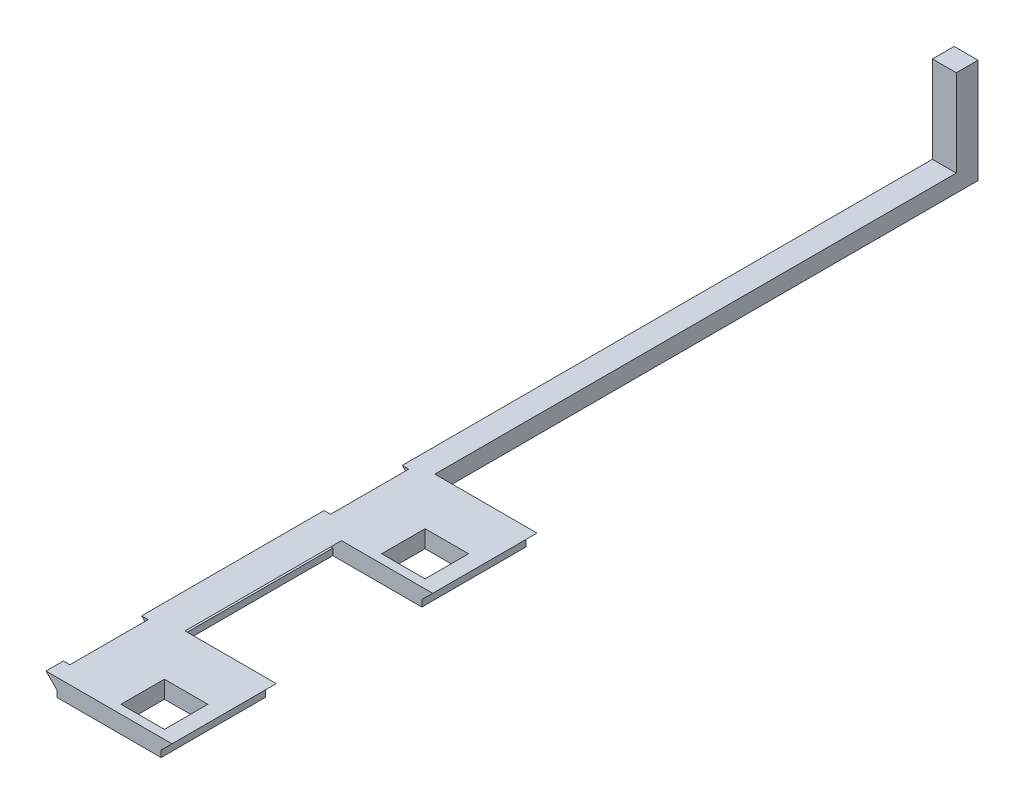
SolidWorks part; units mm, degrees
ref_plane "Płaszczyzna przednia" through (0, 0, 0) normal (0, 0, 1) x (1, 0, 0)
ref_plane "Płaszczyzna górna" through (0, 0, 0) normal (0, 1, 0) x (1, 0, 0)
ref_plane "Płaszczyzna prawa" through (0, 0, 0) normal (1, 0, 0) x (0, 0, -1)
sketch "Szkic6" plane through (0, 0, 0) normal (0, 1, 0) x (1, 0, 0)
  line L0 (9.5, 60) -> (31, 60)
  line L3 (9.5, 24) -> (31, 24)
  line L4 (31, 0) -> (31, 24)
  line L5 (20.25, 24) -> (20.25, 0) construction
  line L6 (2.5, 12) -> (31, 12) construction
  line L9 (31, 60) -> (31, 84)
  line L10 (20.25, 84) -> (20.25, 60) construction
  line L11 (2.5, 72) -> (31, 72) construction
  line L12 (9.5, 60) -> (9.5, 24)
  line L16 (0, 84) -> (0, 0)
  line L17 (6.5, 209) -> (6.5, 84)
  line L18 (6.5, 84) -> (31, 84)
  line L19 (0, 0) -> (31, 0)
  line L21 (0, 84) -> (0, 209)
  line L22 (0, 209) -> (6.5, 209)
  line L25 (0, 146.5) -> (9, 146.5) construction
  line L26 (9.5, 84) -> (31, 84) [skipped]
  point P14 (20.25, 72)
  point P68 (20.25, 12)
  point P281 (4.5, 42)
  point P384 (4.5, 146.5)
  dimension "D1" = 24
  dimension "D2" = 9.5
  dimension "D4" = 60
  dimension "D5" = 31
  dimension "D6" = 209
  dimension "D7" = 6.5
  dimension "D3" = 2
extrude "Dodanie-wyciągnięcie4" add sketch "Szkic6" along normal blind 3
chamfer "Sfazowanie2" distance 3 angle 45 3 edges at (9.5, 0, -42) (31, 0, -72) (31, 0, -12)
fillet "Sfazowanie3" radius 3 1 edges at (0, 0, -104.5) profile chamfer
chamfer "Chamfer1" [suppressed] distance 2 angle 45
sketch "Szkic8" plane through (0, 3, 0) normal (0, 1, 0) x (1, 0, 0)
  line L0 (26.25, 12) -> (26.25, 2)
  line L1 (16.25, 12) -> (16.25, 2)
  line L2 (16.25, 62) -> (26.25, 62)
  line L3 (26.25, 72) -> (16.25, 72)
  line L4 (26.25, 72) -> (26.25, 62)
  line L5 (16.25, 72) -> (16.25, 62)
  line L6 (16.25, 2) -> (26.25, 2)
  line L7 (26.25, 12) -> (16.25, 12)
  line L8 (21.25, 72) -> (21.25, 2) construction
  line L9 (0, 209) -> (0, 0) construction
  line L10 (0, 0) -> (31, 0) construction
  dimension "D1" = 21.25
  dimension "D2" = 10
  dimension "D3" = 10
  dimension "D4" = 60
  dimension "D5" = 2
extrude "Wytnij-wyciągnięcie1" cut sketch "Szkic8" against normal blind 10
sketch "Szkic9" plane through (0, 3, 0) normal (0, 1, 0) x (1, 0, 0)
  line L0 (0, 67) -> (0, 7) construction
  line L2 (0, 67) -> (0, 69) construction
  line L3 (2.5, 82) -> (-2.5, 82)
  line L4 (2.5, 82) -> (2.5, 64)
  line L5 (2.5, 64) -> (-2.5, 64)
  line L6 (-2.5, 82) -> (-2.5, 64)
  line L7 (2.5, 82) -> (-2.5, 64) construction
  line L8 (2.5, 64) -> (-2.5, 82) construction
  line L9 (0, 67) -> (0, 65) construction
  line L10 (0, 7) -> (0, 5) construction
  line L11 (2.5, 22) -> (-2.5, 22)
  line L12 (2.5, 22) -> (2.5, 4)
  line L13 (2.5, 4) -> (-2.5, 4)
  line L14 (-2.5, 22) -> (-2.5, 4)
  line L15 (2.5, 22) -> (-2.5, 4) construction
  line L16 (2.5, 4) -> (-2.5, 22) construction
  line L17 (0, 7) -> (0, 9) construction
  line L18 (0, 209) -> (0, 0) construction
  line L19 (0, 0) -> (31, 0) construction
  circle A2 centre (0, 7) radius 2 construction
  circle A3 centre (0, 67) radius 2 construction
  point P7 (0, 73)
  point P12 (0, 13)
  point P19 (0, 0)
  dimension "D5" = 4
  dimension "D1" = 60
  dimension "D2" = 7
  dimension "D4" = 1
  dimension "D6" = 5
  dimension "D7" = 13
  dimension "D8" = 5
  dimension "D9" = 1
  dimension "D10" = 13
extrude "Wytnij-wyciągnięcie2" cut sketch "Szkic9" against normal blind 10
sketch "Szkic11" plane through (0, 0, 0) normal (0, -1, 0) x (1, 0, 0)
  line L0 (3.5, 0) -> (3.5, -209)
  line L1 (3, 0) -> (28, 0) construction
  line L2 (6.5, -209) -> (3, -209) construction
  line L3 (3.5, -209) -> (6.5, -209)
  line L4 (6.5, -209) -> (6.5, -84)
  line L5 (6.5, -84) -> (27.5, -84)
  line L6 (28, -84) -> (6.5, -84) construction
  line L7 (27.5, -84) -> (27.5, -60)
  line L8 (6.5, -60) -> (28, -60) construction
  line L9 (27.5, -60) -> (7, -60)
  line L10 (7, -60) -> (7, -24)
  line L11 (7, -24) -> (27.5, -24)
  line L12 (28, -24) -> (6.5, -24) construction
  line L13 (27.5, -24) -> (27.5, 0)
  line L14 (27.5, 0) -> (3.5, 0)
  line L15 (6.5, -24) -> (9.5, -24) construction
  line L17 (28, -24) -> (28, 0) construction
  line L19 (28, -84) -> (28, -60) construction
  line L21 (26.25, -12) -> (26.25, -2) construction
  line L22 (26.25, -2) -> (16.25, -2) construction
  line L23 (16.25, -2) -> (16.25, -12) construction
  line L24 (16.25, -12) -> (26.25, -12) construction
  line L25 (26.25, -72) -> (26.25, -62) construction
  line L26 (26.25, -62) -> (16.25, -62) construction
  line L27 (16.25, -62) -> (16.25, -72) construction
  line L28 (16.25, -72) -> (26.25, -72) construction
  line L29 (26.25, -12) -> (26.25, -2)
  line L30 (26.25, -2) -> (16.25, -2)
  line L31 (16.25, -2) -> (16.25, -12)
  line L32 (16.25, -12) -> (26.25, -12)
  line L33 (26.25, -72) -> (26.25, -62)
  line L34 (26.25, -62) -> (16.25, -62)
  line L35 (16.25, -62) -> (16.25, -72)
  line L36 (16.25, -72) -> (26.25, -72)
  point P23 (7, -24)
  point P27 (7, -84)
  dimension "D1" = 3.5
  dimension "D2" = 0.5
  dimension "D4" = 0.5
extrude "Dodanie-wyciągnięcie6" add sketch "Szkic11" along normal blind 1.5
sketch "Szkic13" plane through (0, 0, 0) normal (0, 0, 1) x (1, 0, 0)
  line L0 (3.5, 0) -> (1, 2.5)
  line L1 (1, 2.5) -> (30, 2.5)
  line L2 (30, 2.5) -> (27.5, 0)
  line L3 (0, 3) -> (3, 0) construction
  line L4 (28, 0) -> (31, 3) construction
  line L5 (0, 3) -> (31, 3) construction
  line L6 (3.5, 0) -> (3, 0)
  line L7 (3, 0) -> (0, 3)
  line L8 (0, 3) -> (31, 3)
  line L9 (31, 3) -> (28, 0)
  line L10 (28, 0) -> (27.5, 0)
  dimension "D1" = 0.5
extrude "Wytnij-wyciągnięcie3" cut sketch "Szkic13" against normal blind 270.5 contours L10 L2 L1 L0 L6 L7 L8 L9 body kept at (3.5, 0, 0)
sketch "Szkic14" plane through (0, 2.5, 0) normal (0, 1, 0) x (1, 0, 0)
  line L0 (6.5, 209) -> (6.5, 84) construction
  line L1 (1, 209) -> (6.5, 209)
  line L2 (1, 209) -> (1, 204)
  line L3 (1, 204) -> (6.5, 204)
  line L4 (6.5, 209) -> (6.5, 204)
  dimension "D1" = 5
extrude "Dodanie-wyciągnięcie7" add sketch "Szkic14" along normal blind 20
